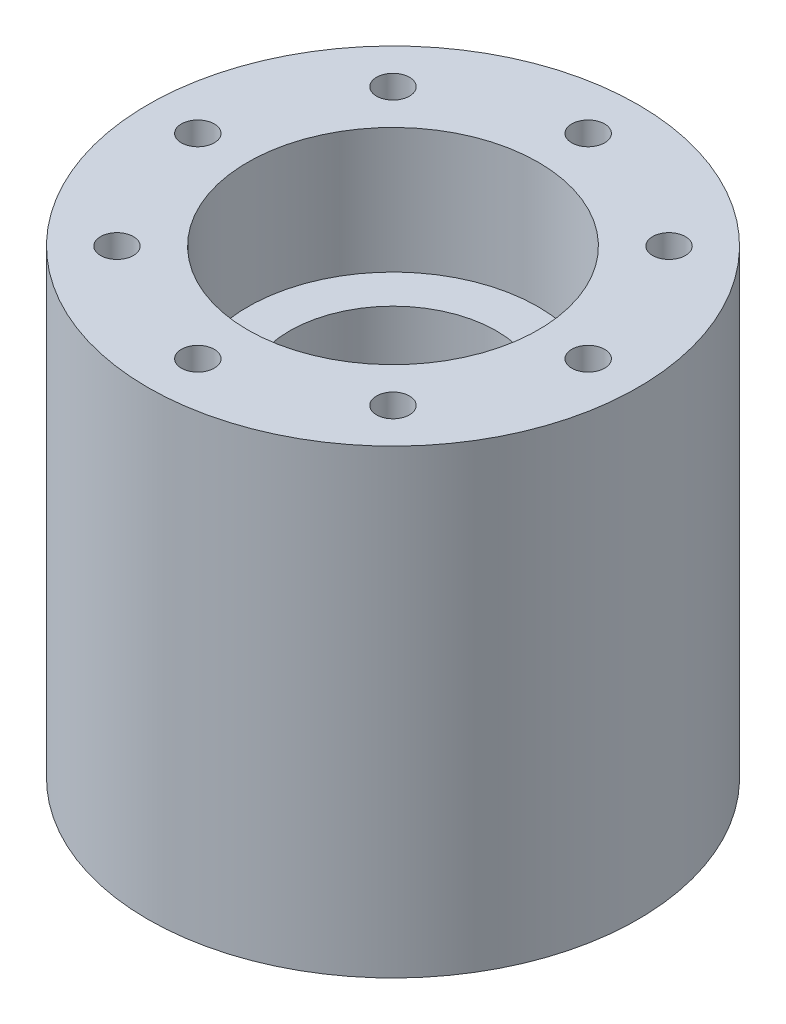
SolidWorks part; units mm, degrees
ref_plane "Top Plane" through (0, 0, 0) normal (0, 0, 1) x (1, 0, 0)
ref_plane "Front Plane" through (0, 0, 0) normal (0, 1, 0) x (1, 0, 0)
ref_plane "Right Plane" through (0, 0, 0) normal (1, 0, 0) x (0, 0, -1)
sketch "Body Sketch" plane through (0, 0, 0) normal (0, 1, 0) x (1, 0, 0)
  circle A0 centre (0, 0) radius 18.6375
  dimension "D1" = 37.275
extrude "Body Extrude" add sketch "Body Sketch" along normal blind 35.0312
sketch "Bearing Pocket Sketch" plane through (0, 0, 0) normal (0, -1, 0) x (-1, 0, 0)
  circle A0 centre (0, 0) radius 11.049
  dimension "D1" = 22.098
extrude "Bearing Pocket Cut 1" cut sketch "Bearing Pocket Sketch" against normal blind 9.525
extrude "Bearing Pocket Cut 2" cut sketch "Bearing Pocket Sketch<2>" along normal blind 9.525 from surface starting at face at (0, 35.0312, 18.6375)
sketch "Bearing Pocket Sketch<2>" plane through (0, 0, 0) normal (0, -1, 0) x (-1, 0, 0) same geometry as "Bearing Pocket Sketch"
sketch "Bore Sketch" plane through (0, 0, 0) normal (0, -1, 0) x (-1, 0, 0)
  circle A0 centre (0, 0) radius 7.874
  circle A1 centre (0, 0) radius 11.049 construction
  circle A2 centre (0, 0) radius 11.049
  dimension "D1" = 3.175
extrude "Bore Cut" cut sketch "Bore Sketch" against normal through all contours A0
sketch "Mounting Hole Sketch 1"
  circle A1 centre (0, 0) radius 11.049 construction
  point P0 (0, -14.8433)
  point P5 (10.4958, -10.4958)
  point P6 (14.8433, 0)
  point P7 (10.4958, 10.4958)
  point P8 (0, 14.8433)
  point P9 (-10.4958, 10.4958)
  point P10 (-14.8433, 0)
  point P11 (-10.4958, -10.4958)
  point P12 (0, 0)
  dimension "D1" = 14.8433
  dimension "D2" = 8
hole_wizard "M3x0.5 Tapped Hole1" positions "3DSketch3" profile "Sketch8" tap size "M3x0.5" standard "ANSI Metric"
sketch3d "3DSketch3"
  point P0 (0, 0, 14.8433)
  point P3 (10.4958, 0, 10.4958)
  point P6 (14.8433, 0, 0)
  point P9 (10.4958, 0, -10.4958)
  point P12 (0, 0, -14.8433)
  point P15 (-10.4958, 0, -10.4958)
  point P18 (-14.8433, 0, 0)
  point P21 (-10.4958, 0, 10.4958)
sketch "Sketch8" plane through (0, 0, 14.8433) normal (1, 0, 0) x (0, 0, -1)
  line L0 (0, 0) -> (0, 8.2517)
  line L1 (0, 8.2517) -> (1.25, 7.5006)
  line L2 (1.25, 7.5006) -> (1.25, 0)
  line L5 (1.25, 0) -> (0, 0)
  line L10 (0, 8.2517) -> (-1.25, 7.5006) construction
  line L11 (0, -6.35) -> (0, 107.95) construction
  dimension "Tap Drill Dia." = 2.5
  dimension "Tap Drill Depth" = 7.5006
  dimension "Drill Angle" = 118
cosmetic thread "Hole Thread3" parameters "D1"=5.9995, "D2"=3
cosmetic thread "Hole Thread4" parameters "D1"=5.9995, "D2"=3
cosmetic thread "Hole Thread5" parameters "D1"=5.9995, "D2"=3
cosmetic thread "Hole Thread6" parameters "D1"=5.9995, "D2"=3
cosmetic thread "Hole Thread7" parameters "D1"=5.9995, "D2"=3
cosmetic thread "Hole Thread8" parameters "D1"=5.9995, "D2"=3
cosmetic thread "Hole Thread9" parameters "D1"=5.9995, "D2"=3
cosmetic thread "Hole Thread10" parameters "D1"=5.9995, "D2"=3
sketch "Mounting Hole Sketch 2" plane through (0, 35.0312, 0) normal (0, 1, 0) x (1, 0, 0)
  point P0 (0, -14.8433)
  point P5 (-10.4958, -10.4958)
  point P6 (-14.8433, 0)
  point P7 (-10.4958, 10.4958)
  point P8 (0, 14.8433)
  point P9 (10.4958, 10.4958)
  point P10 (14.8433, 0)
  point P11 (10.4958, -10.4958)
  point P12 (0, 0)
  dimension "D1" = 14.8433
  dimension "D2" = 8
hole_wizard "M3x0.5 Tapped Hole3" positions "3DSketch4" profile "Sketch13" tap size "M3x0.5" standard "ANSI Metric"
sketch3d "3DSketch4"
  point P0 (0, 35.0312, 14.8433)
  point P3 (10.4958, 35.0312, 10.4958)
  point P6 (14.8433, 35.0312, 0)
  point P9 (10.4958, 35.0312, -10.4958)
  point P12 (0, 35.0312, -14.8433)
  point P15 (-10.4958, 35.0312, -10.4958)
  point P18 (-14.8433, 35.0312, 0)
  point P21 (-10.4958, 35.0312, 10.4958)
sketch "Sketch13" plane through (0, 35.0312, 14.8433) normal (1, 0, 0) x (0, 0, 1)
  line L0 (0, 0) -> (0, 8.2517)
  line L1 (0, 8.2517) -> (1.25, 7.5006)
  line L2 (1.25, 7.5006) -> (1.25, 0)
  line L5 (1.25, 0) -> (0, 0)
  line L10 (0, 8.2517) -> (-1.25, 7.5006) construction
  line L11 (0, -6.35) -> (0, 107.95) construction
  dimension "Tap Drill Dia." = 2.5
  dimension "Tap Drill Depth" = 7.5006
  dimension "Drill Angle" = 118
cosmetic thread "Hole Thread27" parameters "D1"=5.9995, "D2"=3
cosmetic thread "Hole Thread28" parameters "D1"=5.9995, "D2"=3
cosmetic thread "Hole Thread29" parameters "D1"=5.9995, "D2"=3
cosmetic thread "Hole Thread30" parameters "D1"=5.9995, "D2"=3
cosmetic thread "Hole Thread31" parameters "D1"=5.9995, "D2"=3
cosmetic thread "Hole Thread32" parameters "D1"=5.9995, "D2"=3
cosmetic thread "Hole Thread33" parameters "D1"=5.9995, "D2"=3
cosmetic thread "Hole Thread34" parameters "D1"=5.9995, "D2"=3
ref_plane "Cylinder Tanget Plane" through (0, 0, 18.6375) normal (0, 0, 1) x (1, 0, 0)
sketch "Cylinder Center Point Sketch" plane through (0, 0, 18.6375) normal (0, 0, 1) x (1, 0, 0)
  line L0 (-18.6375, 0) -> (18.6375, 0) construction
  line L1 (-18.6375, 0) -> (18.6375, 0) construction
  line L2 (18.6375, 35.0312) -> (-18.6375, 35.0312) construction
  line L3 (18.6375, 35.0312) -> (-18.6375, 35.0312) construction
  line L4 (0, 0) -> (0, 35.0312) construction
  line L5 (-18.6375, 17.5156) -> (18.6375, 17.5156) construction
  point P6 (0, 17.5156)
ref_plane "Cylinder Cross Section Plane" through (0, 17.5156, 0) normal (0, 1, 0) x (1, 0, 0)
sketch "Cylinder Circumference Sketch" plane through (0, 17.5156, 0) normal (0, 1, 0) x (1, 0, 0)
  circle A0 centre (0, 0) radius 18.6375 construction
  circle A1 centre (0, 0) radius 18.6375 construction
equation "\"turing_spool_bearingpocket\"=0.87"
equation "\"D1@Bearing Pocket Sketch\"=\"turing_spool_bearingpocket\""
equation "\"turing_spool_holeradius\"=0.58438"
equation "\"D1@Mounting Hole Sketch 1\"=\"turing_spool_holeradius\""
equation "\"D1@Mounting Hole Sketch 2\"=\"turing_spool_holeradius\""
